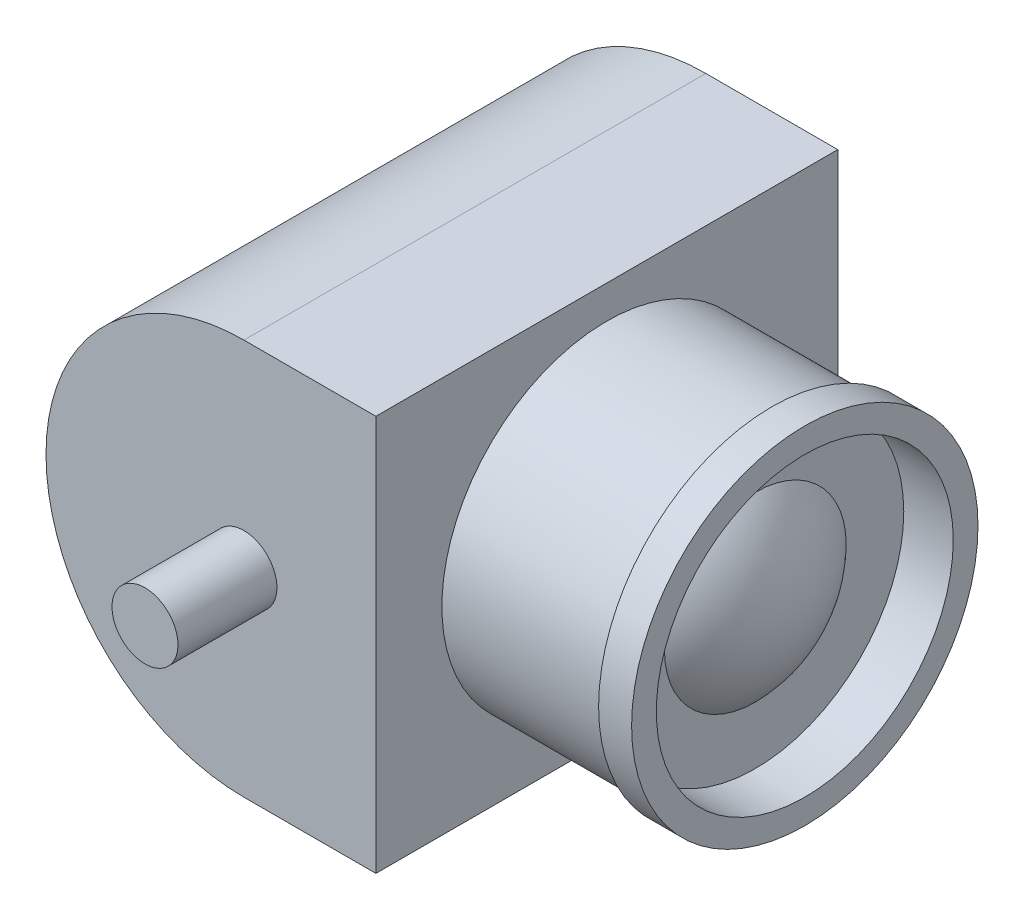
SolidWorks part; units mm, degrees
ref_plane "Front Plane" through (0, 0, 0) normal (0, 0, 1) x (1, 0, 0)
ref_plane "Top Plane" through (0, 0, 0) normal (0, 1, 0) x (1, 0, 0)
ref_plane "Right Plane" through (0, 0, 0) normal (1, 0, 0) x (0, 0, -1)
sketch "Sketch1" plane through (0, 0, 0) normal (1, 0, 0) x (0, 0, -1)
  line L1 (-7, 6) -> (7, 6)
  line L2 (-7, 6) -> (-7, -6)
  line L3 (-7, -6) -> (7, -6)
  line L4 (7, 6) -> (7, -6)
  line L5 (-7, 6) -> (7, -6) construction
  line L6 (-7, -6) -> (7, 6) construction
  point P0 (0, 0)
  dimension "D1" = 14
  dimension "D2" = 12
extrude "Boss-Extrude1" add sketch "Sketch1" along normal blind 10
sketch "Sketch2" plane through (10, 0, 0) normal (1, 0, 0) x (0, 0, -1)
  circle A0 centre (0, 0) radius 5
  dimension "D1" = 10
extrude "Boss-Extrude2" add sketch "Sketch2" along normal blind 5
sketch "Sketch3" plane through (15, 0, 0) normal (1, 0, 0) x (0, 0, -1)
  circle A0 centre (0, 0) radius 5.25
  dimension "D1" = 10.5
extrude "Boss-Extrude3" add sketch "Sketch3" along normal blind 1
sketch "Sketch5" plane through (16, 0, 0) normal (1, 0, 0) x (0, 0, -1)
  circle A0 centre (0, 0) radius 4.5
  dimension "D1" = 9
extrude "Cut-Extrude1" cut sketch "Sketch5" against normal blind 1.5
sketch "Sketch6" plane through (0, 0, 0) normal (0, 1, 0) x (1, 0, 0)
  line L0 (10, 7) -> (10, -7) construction
  line L1 (15.596, -0.1782) -> (15.596, 0)
  line L2 (15.596, 0) -> (15.6, 0)
  line L3 (11.6, 0) -> (15.6, 0)
  line L4 (11.6, 0) -> (11.6, 4)
  arc A0 (15.6, 0) -> (11.6, 4) centre (11.6, 0) ccw
  dimension "D1" = 8
  dimension "D2" = 1.6
revolve "Revolve2" add sketch "Sketch6" angle 360 about L3
fillet "Fillet1" radius 6 2 edges at (0, -6, 0) (0, 6, 0)
sketch "Sketch11" plane through (0, 0, 0) normal (0, 0, 1) x (1, 0, 0)
  circle A0 centre (6, 0) radius 1
  dimension "D1" = 2
extrude "Boss-Extrude4" add sketch "Sketch11" along normal mid plane 20
